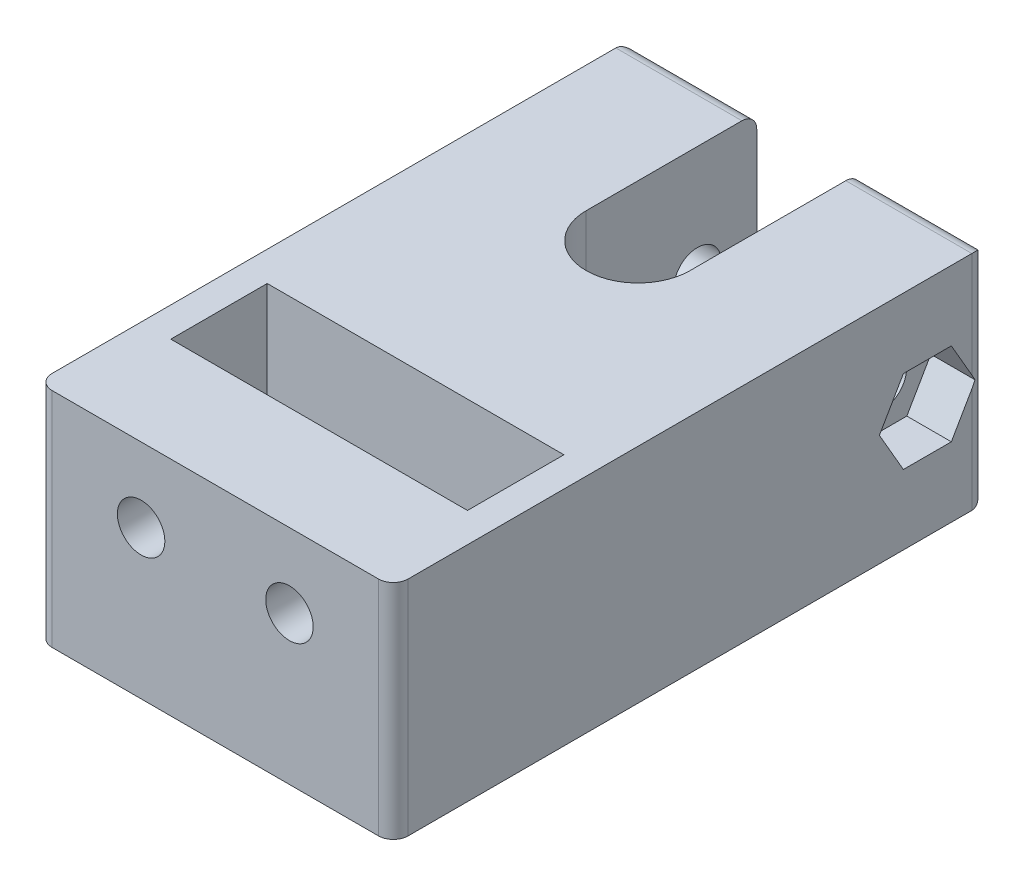
SolidWorks part; units mm, degrees
ref_plane "Alzado" through (0, 0, 0) normal (0, 0, 1) x (1, 0, 0)
ref_plane "Planta" through (0, 0, 0) normal (0, 1, 0) x (1, 0, 0)
ref_plane "Vista lateral" through (0, 0, 0) normal (1, 0, 0) x (0, 0, -1)
sketch "Croquis1" plane through (0, 0, 0) normal (0, 1, 0) x (1, 0, 0)
  line L0 (0, 0) -> (0, 15) construction
  line L1 (-12, -20) -> (12, -20)
  line L2 (-12, -20) -> (-12, 20)
  line L3 (-12, 20) -> (-3.5, 20)
  line L4 (12, -20) -> (12, 20)
  line L5 (-12, -20) -> (12, 20) construction
  line L6 (-12, 20) -> (12, -20) construction
  line L9 (3.5, 20) -> (12, 20)
  line L10 (-3.5, 8.5) -> (-3.5, 20)
  line L11 (3.5, 8.5) -> (3.5, 20)
  arc A0 (-3.5, 8.5) -> (3.5, 8.5) centre (0, 8.5) ccw
  point P0 (0, 0)
  dimension "D1" = 7
  dimension "D2" = 24
  dimension "D3" = 40
  dimension "D4" = 8
extrude "Saliente-Extruir2" add sketch "Croquis1" along normal blind 15
sketch "Croquis3" plane through (0, 0, 0) normal (1, 0, 0) x (0, 0, -1)
  line L0 (20, 15) -> (20, 0) construction
  circle A0 centre (16, 7.5) radius 1.6
  dimension "D1" = 3.2
  dimension "D2" = 4
  dimension "D3" = 7.5
extrude "Cortar-Extruir2" cut sketch "Croquis3" against normal through all both and the other way through all
sketch "Croquis4" plane through (0, 15, 0) normal (0, 1, 0) x (1, 0, 0)
  line L0 (-12, -20) -> (12, -20) construction
  line L1 (-10, -6.5) -> (10, -6.5)
  line L2 (-10, -6.5) -> (-10, -13)
  line L3 (-10, -13) -> (10, -13)
  line L4 (10, -6.5) -> (10, -13)
  line L5 (-10, -6.5) -> (10, -13) construction
  line L6 (-10, -13) -> (10, -6.5) construction
  line L7 (-12, 20) -> (-12, -20) construction
  point P0 (0, -9.75)
  point P9 (0, 0)
  dimension "D1" = 7
  dimension "D2" = 2
  dimension "D3" = 6.5
extrude "Cortar-Extruir3" cut sketch "Croquis4" against normal through all
sketch "Croquis5" plane through (0, 0, 20) normal (0, 0, 1) x (1, 0, 0)
  line L0 (0, 0) -> (0, 15) construction
  line L1 (-12, 15) -> (12, 15) construction
  circle A0 centre (-5, 10) radius 1.6
  circle A1 centre (5, 10) radius 1.6
  point P9 (0, 0)
  dimension "D2" = 3.2
  dimension "D1" = 10
  dimension "D3" = 5
extrude "Cortar-Extruir4" cut sketch "Croquis5" against normal up to next
sketch "Croquis6" plane through (0, 0, 13) normal (0, 0, -1) x (-1, 0, 0)
  line L1 (-3.3834, 12.8) -> (-6.6166, 12.8)
  line L2 (-6.6166, 12.8) -> (-8.2332, 10)
  line L3 (-8.2332, 10) -> (-6.6166, 7.2)
  line L4 (-6.6166, 7.2) -> (-3.3834, 7.2)
  line L5 (-3.3834, 7.2) -> (-1.7668, 10)
  line L6 (-1.7668, 10) -> (-3.3834, 12.8)
  line L13 (6.6166, 12.8) -> (3.3834, 12.8)
  line L14 (3.3834, 12.8) -> (1.7668, 10)
  line L15 (1.7668, 10) -> (3.3834, 7.2)
  line L16 (3.3834, 7.2) -> (6.6166, 7.2)
  line L17 (6.6166, 7.2) -> (8.2332, 10)
  line L18 (8.2332, 10) -> (6.6166, 12.8)
  circle A0 centre (-5, 10) radius 2.8 construction
  circle A1 centre (5, 10) radius 2.8 construction
  dimension "D1" = 5.6
extrude "Cortar-Extruir5" cut sketch "Croquis6" against normal blind 3
sketch "Croquis7" plane through (12, 0, 0) normal (1, 0, 0) x (0, 0, -1)
  line L1 (17.6166, 4.7) -> (19.2332, 7.5)
  line L2 (19.2332, 7.5) -> (17.6166, 10.3)
  line L3 (17.6166, 10.3) -> (14.3834, 10.3)
  line L4 (14.3834, 10.3) -> (12.7668, 7.5)
  line L5 (12.7668, 7.5) -> (14.3834, 4.7)
  line L6 (14.3834, 4.7) -> (17.6166, 4.7)
  circle A0 centre (16, 7.5) radius 2.8 construction
  circle A1 centre (16, 7.5) radius 1.6 construction
  point P1 (0, 0)
  dimension "D1" = 5.6
extrude "Cortar-Extruir6" cut sketch "Croquis7" against normal blind 3
fillet "Redondeo1" radius 1 8 edges at (-12, 7.5, 20) (-12, 7.5, -20) (12, 7.5, -20) (12, 7.5, 20) (-7.75, 15, -20) (7.75, 15, -20) (-7.75, 0, -20) (7.75, 0, -20)
equation "\"¿\"=1"
